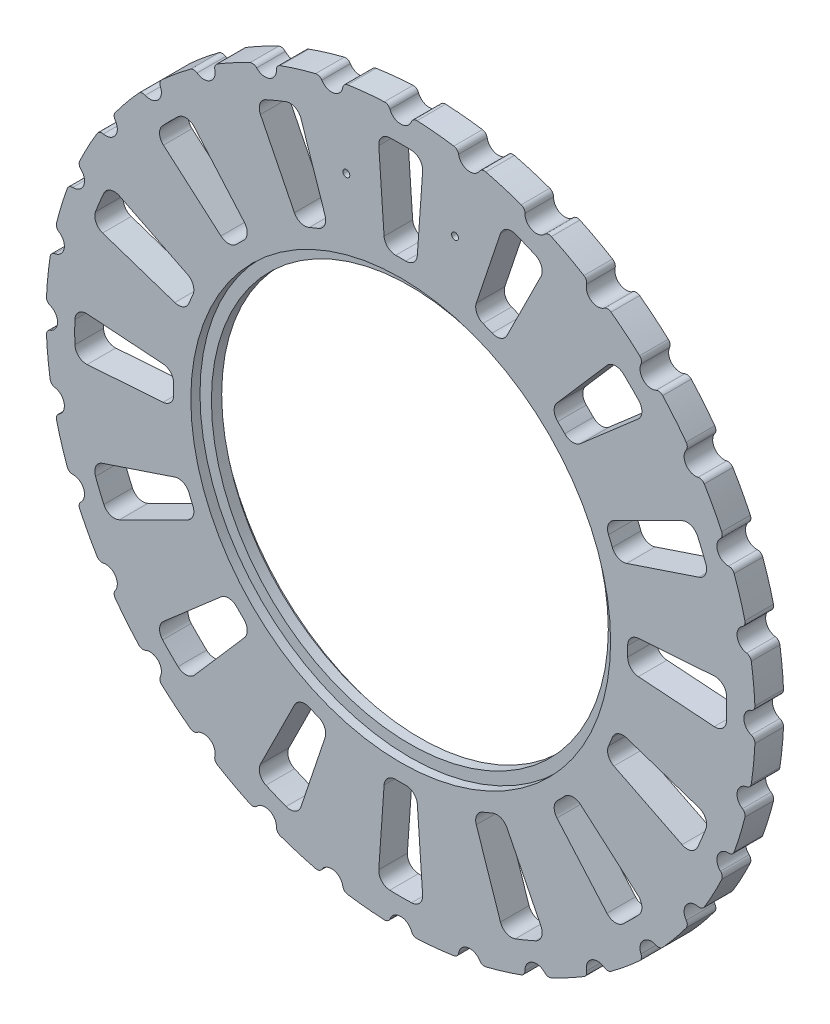
SolidWorks part; units mm, degrees
ref_plane "前视基准面" through (0, 0, 0) normal (0, 0, 1) x (1, 0, 0)
ref_plane "上视基准面" through (0, 0, 0) normal (0, 1, 0) x (1, 0, 0)
ref_plane "右视基准面" through (0, 0, 0) normal (1, 0, 0) x (0, 0, -1)
other "Configuration Table"
sketch "草图1" plane through (0, 0, 0) normal (0, 0, 1) x (1, 0, 0)
  line L2 (0, 62) -> (0, 0) construction
  circle A0 centre (0, 0) radius 62
  circle A1 centre (0, 62) radius 2
  dimension "D1" = 124
  dimension "D2" = 4
extrude "凸台-拉伸1" add sketch "草图1" along normal blind 5 contours A0
extrude "切除-拉伸1" cut sketch "草图1<3>" along normal through all contours A1
sketch "草图1<3>" plane through (0, 0, 0) normal (0, 0, 1) x (1, 0, 0) same geometry as "草图1"
fillet "圆角1" radius 1 2 edges at (1.9997, 61.9677, 2.5) (-1.9997, 61.9677, 2.5)
pattern_circular "阵列(圆周)1" count 32 over 360 about axis through (0, 0, 5) along (0, 0, -1) of "切除-拉伸1", "圆角1"
sketch "草图3" plane through (0, 0, 0) normal (0, 0, -1) x (-1, 0, 0)
  circle A1 centre (0, 0) radius 34.7
  dimension "D1" = 69.4
extrude "切除-拉伸2" cut sketch "草图3" against normal through all
sketch "草图4" plane through (0, 0, 0) normal (0, 0, -1) x (-1, 0, 0)
  circle A0 centre (0, 0) radius 36.7
  circle A1 centre (0, 0) radius 34.7 construction
  dimension "D1" = 2
extrude "切除-拉伸3" cut sketch "草图4" against normal blind 1.6
extrude "切除-拉伸5" cut sketch "草图4<2>" along normal blind 1.6 from surface starting at face at (-34.7, 0, 5)
sketch "草图4<2>" plane through (0, 0, 0) normal (0, 0, -1) x (-1, 0, 0) same geometry as "草图4"
sketch "草图8" plane through (0, 0, 0) normal (0, 0, -1) x (-1, 0, 0)
  line L0 (0, 0) -> (0, 75.4294) construction
  line L1 (0, 0) -> (-4.3249, -61.849)
  line L2 (0, 0) -> (4.2044, -60.126)
  arc A3 (-21.0675, -58.3109) -> (-14.8788, -60.1882) centre (0, 0) ccw construction
  circle A4 centre (0, 0) radius 39.7
  circle A5 centre (0, 0) radius 57
  arc A6 (-49.9128, -36.7792) -> (-45.81, -41.7785) centre (0, 0) ccw construction
  circle A7 centre (0, 0) radius 36.7 construction
  dimension "D3" = 5
  dimension "D4" = 3
  dimension "D1" = 4
  dimension "D2" = 4
extrude "切除-拉伸7" cut sketch "草图8" against normal through all both and the other way through all contours A5 L0 A4 L1 | L0 A5 L2 A4 region at (0, -48.8262, 0)
fillet "圆角3" radius 2 2 edges at (3.9761, -56.8612, 2.5) (-3.9761, -56.8612, 2.5)
fillet "圆角4" radius 2 2 edges at (2.7693, -39.6033, 2.5) (-2.7693, -39.6033, 2.5)
pattern_circular "阵列(圆周)2" count 16 over 360 about axis through (0, 0, 5) along (0, 0, -1) of "切除-拉伸7", "圆角3", "圆角4"
sketch "草图9" plane through (0, 0, 0) normal (0, 0, -1) x (-1, 0, 0)
  line L0 (0, 62) -> (0, 36.7) construction
  line L1 (-9.5, 47.7597) -> (9.5, 47.7597) construction
  line L2 (-12.0956, 60.8087) -> (0, 0) construction
  line L3 (0, 0) -> (12.0956, 60.8087) construction
  circle A0 centre (0, 0) radius 36.7 construction
  arc A2 (-13.7911, 59.7479) -> (-10.1232, 60.4774) centre (-12.0956, 60.8087) ccw construction
  arc A3 (10.1232, 60.4774) -> (13.7911, 59.7479) centre (12.0956, 60.8087) ccw construction
  arc A4 (-1.8699, 61.2903) -> (1.8699, 61.2903) centre (0, 62) ccw construction
  circle A5 centre (-9.5, 47.7597) radius 0.6
  circle A6 centre (9.5, 47.7597) radius 0.6
  dimension "D1" = 1.2
  dimension "D2" = 1.2
  dimension "D3" = 19
extrude "切除-拉伸8" cut sketch "草图9" against normal through all
